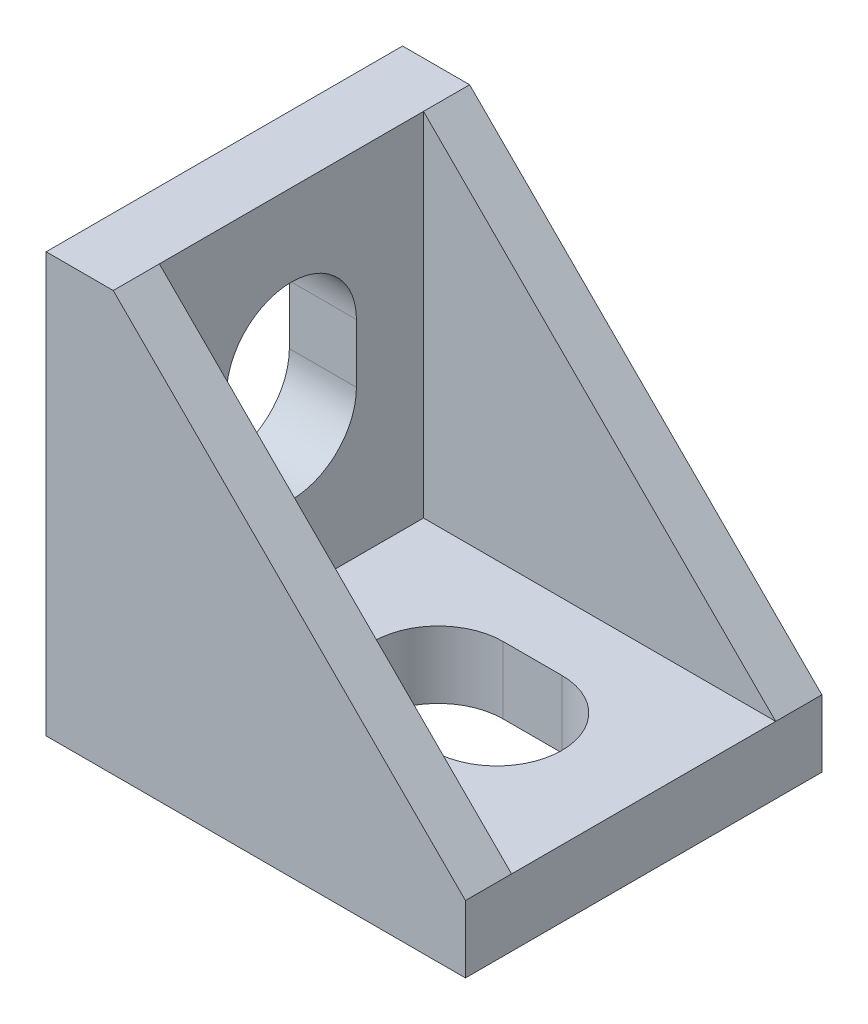
SolidWorks part; units mm, degrees
ref_plane "前视基准面" through (0, 0, 0) normal (0, 0, 1) x (1, 0, 0)
ref_plane "上视基准面" through (0, 0, 0) normal (0, 1, 0) x (1, 0, 0)
ref_plane "右视基准面" through (0, 0, 0) normal (1, 0, 0) x (0, 0, -1)
sketch "草图1" plane through (0, 0, 0) normal (0, 0, 1) x (1, 0, 0)
  line L1 (-10, -10) -> (10, -10)
  line L2 (-10, -10) -> (-10, 10)
  line L3 (-10, 10) -> (10, 10)
  line L4 (10, -10) -> (10, 10)
  line L5 (0, 10) -> (0, -10) construction
  line L6 (-10, 0) -> (10, 0) construction
  point P0 (0, 0)
extrude "凸台-拉伸1" add sketch "草图1" along normal blind 17
sketch "草图2" plane through (0, 10, 0) normal (0, 1, 0) x (1, 0, 0)
  line L0 (10, 0) -> (10, -2.2)
  line L1 (10, -17) -> (10, 0) construction
  line L2 (10, -17) -> (10, -14.8)
  line L3 (10, -14.8) -> (-6.8, -14.8)
  line L4 (-6.8, -14.8) -> (-6.8, -2.2)
  line L5 (-6.8, -2.2) -> (10, -2.2)
  line L6 (10, -14.8) -> (10, -2.2)
  line M5 (10, -17) -> (10, 0)
extrude "切除-拉伸1" cut sketch "草图2" against normal blind 16.8 contours L5 L4 L3 M5 region at (1.6, 10, 8.5)
sketch "草图3" plane through (0, 0, 2.2) normal (0, 0, 1) x (1, 0, 0)
  line L0 (-6.8, 10) -> (10, -6.8)
  line L1 (10, -6.8) -> (10, 10)
  line L2 (10, 10) -> (-6.8, 10)
extrude "切除-拉伸2" cut sketch "草图3" against normal blind 16.8 and the other way blind 16.8
sketch "草图4" plane through (-6.8, 0, 0) normal (1, 0, 0) x (0, 0, -1)
  line L3 (-5.4, 0.2) -> (-5.4, 3)
  line L5 (-11.6, 0.2) -> (-11.6, 3)
  arc A0 (-11.6, 0.2) -> (-5.4, 0.2) centre (-8.5, 0.2) ccw
  arc A1 (-11.6, 3) -> (-5.4, 3) centre (-8.5, 3) cw
extrude "切除-拉伸3" cut sketch "草图4" against normal blind 16.8
ref_point "点1"
ref_plane "基准面4" through (0, 0, 0) normal (0.7071, -0.7071, 0) x (0, 0, -1)
mirror "镜向1" about plane through (0, 0, 0) normal (0.7071, -0.7071, 0) of "切除-拉伸3"
